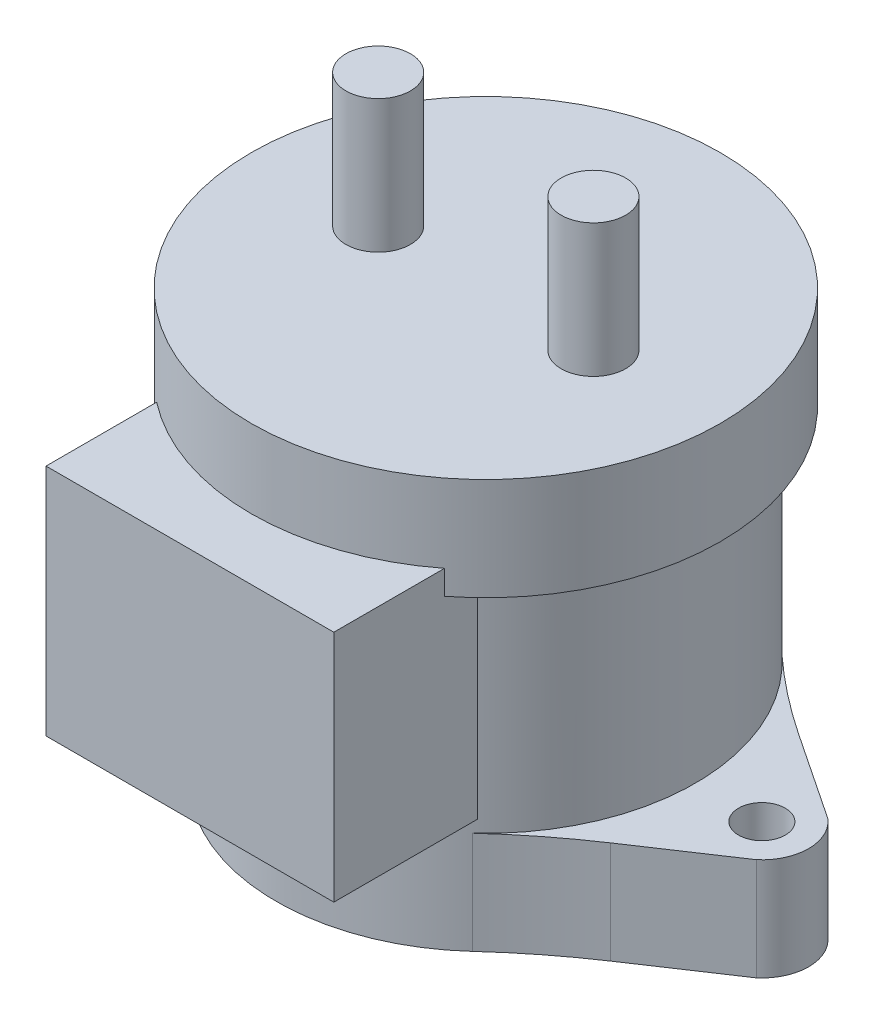
SolidWorks part; units mm, degrees
ref_plane "Front Plane" through (0, 0, 0) normal (0, 0, 1) x (1, 0, 0)
ref_plane "Top Plane" through (0, 0, 0) normal (0, 1, 0) x (1, 0, 0)
ref_plane "Right Plane" through (0, 0, 0) normal (1, 0, 0) x (0, 0, -1)
sketch "Sketch1" plane through (0, 0, 0) normal (0, 1, 0) x (1, 0, 0)
  circle A0 centre (0, 0) radius 26
extrude "Boss-Extrude1" add sketch "Sketch1" along normal blind 14.2
sketch "Sketch4" plane through (0, 0, 0) normal (0, -1, 0) x (1, 0, 0)
  line L1 (0, 26) -> (0, -26) construction
  line L2 (27.1291, -11.6796) -> (37.9901, -4.433)
  line L3 (27.1291, 11.6796) -> (37.9901, 4.433)
  line L4 (-27.1291, 11.6796) -> (-37.9901, 4.433)
  line L5 (-27.1291, -11.6796) -> (-37.9901, -4.433)
  circle A0 centre (0, 0) radius 26 construction
  arc A11 (-17.5451, -19.1878) -> (17.5451, -19.1878) centre (0, 0) ccw
  arc A15 (17.5451, 19.1878) -> (-17.5451, 19.1878) centre (0, 0) ccw
  circle A20 centre (34.25, 0) radius 2.9
  arc A21 (37.9901, -4.433) -> (37.9901, 4.433) centre (34.25, 0) ccw
  arc A22 (17.5451, -19.1878) -> (27.1291, -11.6796) centre (71.53, -78.227) cw
  arc A23 (17.5451, 19.1878) -> (27.1291, 11.6796) centre (71.53, 78.227) ccw
  arc A24 (-37.9901, -4.433) -> (-37.9901, 4.433) centre (-34.25, 0) cw
  circle A25 centre (34.25, 0) radius 5.8 construction
  circle A26 centre (-34.25, 0) radius 2.9
  arc A27 (-17.5451, 19.1878) -> (-27.1291, 11.6796) centre (-71.53, 78.227) cw
  arc A28 (-17.5451, -19.1878) -> (-27.1291, -11.6796) centre (-71.53, -78.227) ccw
  point P10 (0, 0)
  point P21 (40.05, 0)
extrude "Boss-Extrude2" add sketch "Sketch4" against normal blind 12.7
sketch "Sketch6" plane through (0, 14.2, 0) normal (0, 1, 0) x (1, 0, 0)
  line L8 (-17.85, -26.5636) -> (-17.85, -18.9044)
  line L9 (17.85, -26.7996) -> (17.85, -18.9044)
  line L10 (-17.85, -26.7996) -> (-17.85, -26.5636)
  line L12 (0, -36.7) -> (-17.85, -36.7)
  line L13 (-17.85, -26.7996) -> (-17.85, -36.7)
  line L14 (17.85, -26.7996) -> (17.85, -36.7)
  line L15 (0, -36.7) -> (17.85, -36.7)
  arc A2 (-17.85, -18.9044) -> (17.85, -18.9044) centre (0, 0) ccw
  point P8 (0, 0)
extrude "Boss-Extrude3" add sketch "Sketch6" along normal blind 29 separate body
sketch "Sketch8" plane through (0, 14.2, 0) normal (0, 1, 0) x (1, 0, 0)
  circle A0 centre (0, 0) radius 26
extrude "Boss-Extrude4" add sketch "Sketch8" along normal blind 26
sketch "Sketch9" plane through (0, 40.2, 0) normal (0, 1, 0) x (1, 0, 0)
  circle A0 centre (0, 0) radius 29.1
extrude "Boss-Extrude5" add sketch "Sketch9" along normal blind 12.7
sketch "Sketch10" plane through (0, 52.9, 0) normal (0, 1, 0) x (1, 0, 0)
  circle A1 centre (13.35, 0) radius 4
  circle A2 centre (-13.35, 0) radius 4
  point P8 (0, 0)
extrude "Boss-Extrude6" add sketch "Sketch10" along normal blind 16.5
